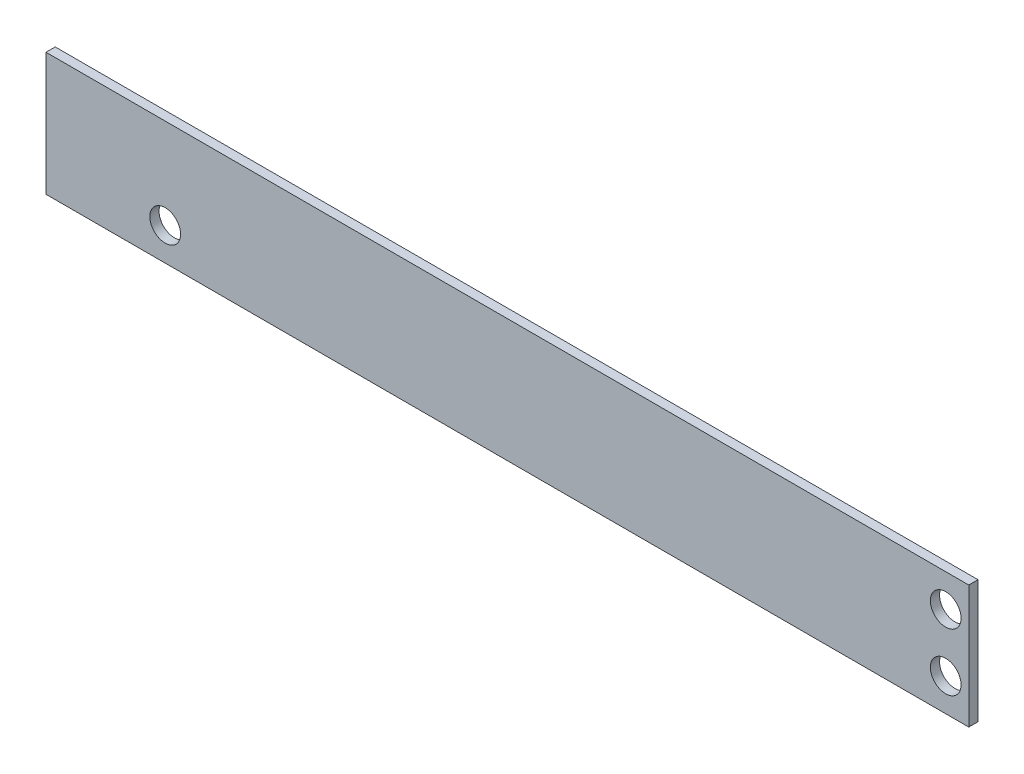
SolidWorks part; units mm, degrees
ref_plane "Front Plane" through (0, 0, 0) normal (0, 0, 1) x (1, 0, 0)
ref_plane "Top Plane" through (0, 0, 0) normal (0, 1, 0) x (1, 0, 0)
ref_plane "Right Plane" through (0, 0, 0) normal (1, 0, 0) x (0, 0, -1)
ref_axis "lens_axis" through (0, 0, 0) along (0, 0, 1)
sketch "dimension" plane through (0, 0, 0) normal (0, 0, 1) x (1, 0, 0)
  line L0 (4, 4) -> (4, -4) construction
  line L1 (-27.5, 4) -> (32.5, 4)
  line L2 (-27.5, 4) -> (-27.5, -4)
  line L3 (-27.5, -4) -> (32.5, -4)
  line L4 (32.5, 4) -> (32.5, -4)
  line L5 (-4, 4) -> (-4, -4) construction
  line L6 (-4, 4) -> (4, -4) construction
  line L7 (-27.5, 0) -> (32.5, 0) construction
  line L8 (-23.7, 4) -> (-23.7, -4)
  line L9 (-28, 4) -> (-28, -4)
  line L10 (-28, 4) -> (-27.5, 4) construction
  line L11 (-28, -4) -> (-27.5, -4) construction
  circle A0 centre (31, 1.875) radius 1
  circle A1 centre (31, -1.875) radius 1
  circle A2 centre (-19.75, -1.875) radius 1
  dimension "D6" = 2
  dimension "D9" = 7.75
  dimension "D1" = 60
  dimension "D2" = 8
  dimension "D3" = 31.5
  dimension "D4" = 36.5
  dimension "D5" = 8
  dimension "D7" = 1.5
  dimension "D8" = 3.75
  dimension "D10" = 4.3
  dimension "D11" = 0.5
sketch "Sketch2" plane through (0, 0, 0) normal (0, 0, 1) x (1, 0, 0)
  line L0 (-27.5, 4) -> (32.5, 4) construction
  line L1 (-27.5, 4) -> (-27.5, -4) construction
  line L2 (-27.5, -4) -> (32.5, -4) construction
  line L3 (32.5, 4) -> (32.5, -4) construction
  line L4 (-27.5, 4) -> (32.5, 4)
  line L5 (-27.5, 4) -> (-27.5, -4)
  line L6 (-27.5, -4) -> (32.5, -4)
  line L7 (32.5, 4) -> (32.5, -4)
  circle A0 centre (-19.75, -1.875) radius 1 construction
  circle A1 centre (31, 1.875) radius 1 construction
  circle A2 centre (31, -1.875) radius 1 construction
  circle A3 centre (-19.75, -1.875) radius 1
  circle A4 centre (31, 1.875) radius 1
  circle A5 centre (31, -1.875) radius 1
extrude "board" add sketch "Sketch2" along normal blind 0.6
